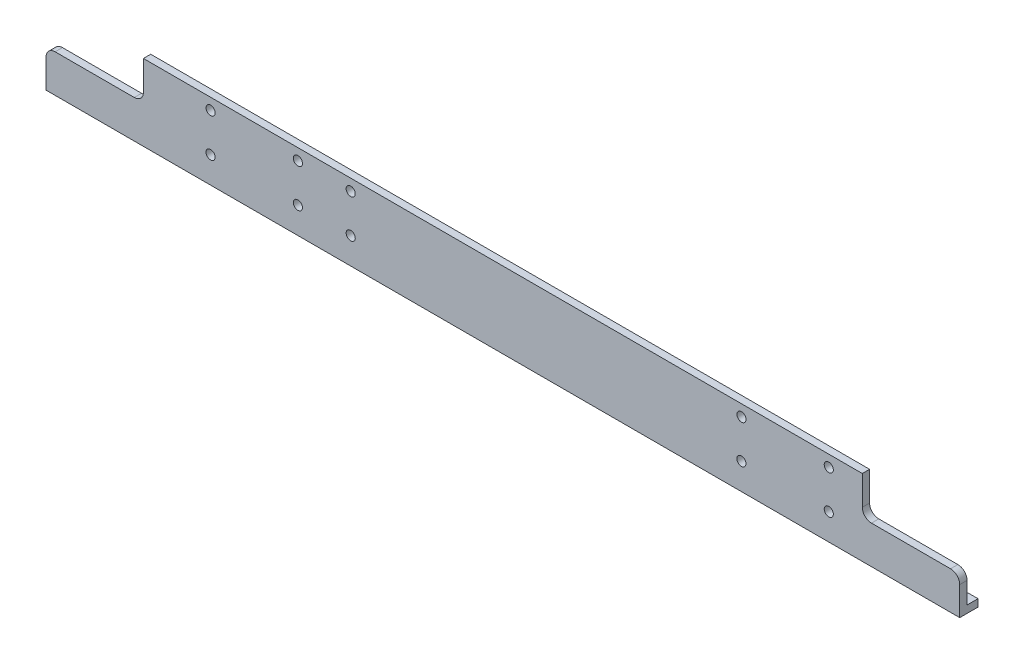
SolidWorks part; units mm, degrees
ref_plane "Front" through (0, 0, 0) normal (0, 0, 1) x (1, 0, 0)
ref_plane "Top" through (0, 0, 0) normal (0, 1, 0) x (1, 0, 0)
ref_plane "Right" through (0, 0, 0) normal (1, 0, 0) x (0, 0, -1)
ref_axis "side-side" through (80.9, 0, 0) along (-1, 0, 0)
ref_axis "up-down" through (0, 50, 0) along (0, -1, 0)
ref_axis "front-back" through (0, 0, -80.9) along (0, 0, 1)
sketch "Sketch1" plane through (0, 0, 0) normal (1, 0, 0) x (0, 0, -1)
  line L1 (0, 0) -> (31.75, 0)
  line L2 (0, 0) -> (0, 31.75)
  line L3 (0, 31.75) -> (3.048, 31.75)
  line L4 (31.75, 0) -> (31.75, 3.048)
  line L5 (3.048, 3.048) -> (31.75, 3.048)
  line L6 (3.048, 3.048) -> (3.048, 31.75)
  dimension "D1" = 31.75
  dimension "D2" = 3.048
extrude "Boss-Extrude1" add sketch "Sketch1" along normal mid plane 381
sketch "Sketch2" plane through (0, 0, 0) normal (0, 0, 1) x (1, 0, 0)
  line L2 (152.877, 19.5) -> (185.5, 19.5)
  line L3 (149.877, 32) -> (149.877, 22.5)
  line L6 (174.5, 4) -> (174.5, 0)
  line L7 (172.5, 4) -> (174.5, 4)
hole_wizard "#6 Clearance Hole1" positions "Sketch4" profile "Sketch3" hole size "#6" standard "ANSI Inch" end condition through all
sketch "Sketch4" plane through (0, 0, 0) normal (0, 0, 1) x (1, 0, 0)
  point P0 (135.9, 27)
  point P3 (135.9, 11)
  point P6 (99.5, 27)
  point P9 (99.468, 11)
  point P12 (-121.868, 27)
  point P15 (-121.868, 11)
  point P18 (-85.468, 11)
  point P21 (-85.468, 27)
sketch "Sketch3" plane through (135.9, 27, 0) normal (1, 0, 0) x (0, -1, 0)
  line L0 (0, 0) -> (0, 31.75)
  line L1 (0, 31.75) -> (1.8986, 31.75)
  line L2 (1.8986, 31.75) -> (1.8986, 0)
  line L5 (1.8986, 0) -> (0, 0)
  line L11 (0, -6.35) -> (0, 107.95) construction
  dimension "Thru Hole Dia." = 3.7973
  dimension "Thru Hole Depth" = 31.75
sketch "Sketch5" plane through (0, 0, 0) normal (0, 0, 1) x (1, 0, 0)
  line L0 (149.877, 32) -> (149.877, 22.5) construction
  line L2 (149.877, 41.148) -> (149.877, 19.558)
  line L3 (153.687, 15.748) -> (186.69, 15.748)
  line L4 (0, 0) -> (0, 88.4721) construction
  line L5 (190.5, 31.75) -> (190.5, 0) construction
  line L6 (190.5, 11.938) -> (190.5, -9.652)
  line L7 (190.5, 0) -> (-190.5, 0) construction
  line L8 (-198.12, 41.148) -> (-149.877, 41.148)
  line L9 (198.12, -9.652) -> (190.5, -9.652)
  line L10 (198.12, -9.652) -> (198.12, 41.148)
  line L11 (198.12, 41.148) -> (149.877, 41.148)
  line L12 (-198.12, -9.652) -> (-198.12, 41.148)
  line L13 (-198.12, -9.652) -> (-190.5, -9.652)
  line L14 (-190.5, 11.938) -> (-190.5, -9.652)
  line L15 (-153.687, 15.748) -> (-186.69, 15.748)
  line L16 (-149.877, 41.148) -> (-149.877, 19.558)
  arc A0 (149.877, 19.558) -> (153.687, 15.748) centre (153.687, 19.558) ccw
  arc A1 (190.5, 11.938) -> (186.69, 15.748) centre (186.69, 11.938) ccw
  arc A2 (-190.5, 11.938) -> (-186.69, 15.748) centre (-186.69, 11.938) cw
  arc A3 (-149.877, 19.558) -> (-153.687, 15.748) centre (-153.687, 19.558) cw
  dimension "D1" = 3.81
  dimension "D3" = 3.81
  dimension "D2" = 15.748
  dimension "D4" = 25.4
  dimension "D5" = 7.62
  dimension "D6" = 25.4
extrude "Cut-Extrude1" cut sketch "Sketch5" against normal through all
sketch "Sketch6" plane through (0, 0, 0) normal (1, 0, 0) x (0, 0, -1)
  line L0 (0, 50) -> (0, -50) construction
  line L1 (7.62, 7.62) -> (33.02, 7.62)
  line L2 (7.62, 7.62) -> (7.62, -7.62)
  line L3 (7.62, -7.62) -> (33.02, -7.62)
  line L4 (33.02, 7.62) -> (33.02, -7.62)
  line L5 (50, 0) -> (-50, 0) construction
  dimension "D1" = 7.62
  dimension "D2" = 25.4
  dimension "D3" = 7.62
  dimension "D4" = 7.62
extrude "Cut-Extrude2" cut sketch "Sketch6" against normal through all and the other way through all
sketch "Sketch7" plane through (0, 0, 0) normal (0, 0, 1) x (1, 0, 0)
  circle A2 centre (-63.448, 27) radius 1.3525
  circle A3 centre (-63.448, 11) radius 1.3525
  circle A4 centre (-85.468, 27) radius 1.8986 construction
  dimension "D1" = 22.02
hole_wizard "#6 Clearance Hole2" positions "Sketch9" profile "Sketch8" hole size "#6" standard "ANSI Inch" end condition through all
sketch "Sketch9" plane through (0, 0, 0) normal (0, 0, 1) x (1, 0, 0)
  point P0 (-63.448, 27)
  point P3 (-63.448, 11)
sketch "Sketch8" plane through (-63.448, 27, 0) normal (1, 0, 0) x (0, -1, 0)
  line L0 (0, 0) -> (0, 7.62)
  line L1 (0, 7.62) -> (1.8986, 7.62)
  line L2 (1.8986, 7.62) -> (1.8986, 0)
  line L5 (1.8986, 0) -> (0, 0)
  line L11 (0, -6.35) -> (0, 107.95) construction
  dimension "Thru Hole Dia." = 3.7973
  dimension "Thru Hole Depth" = 7.62
